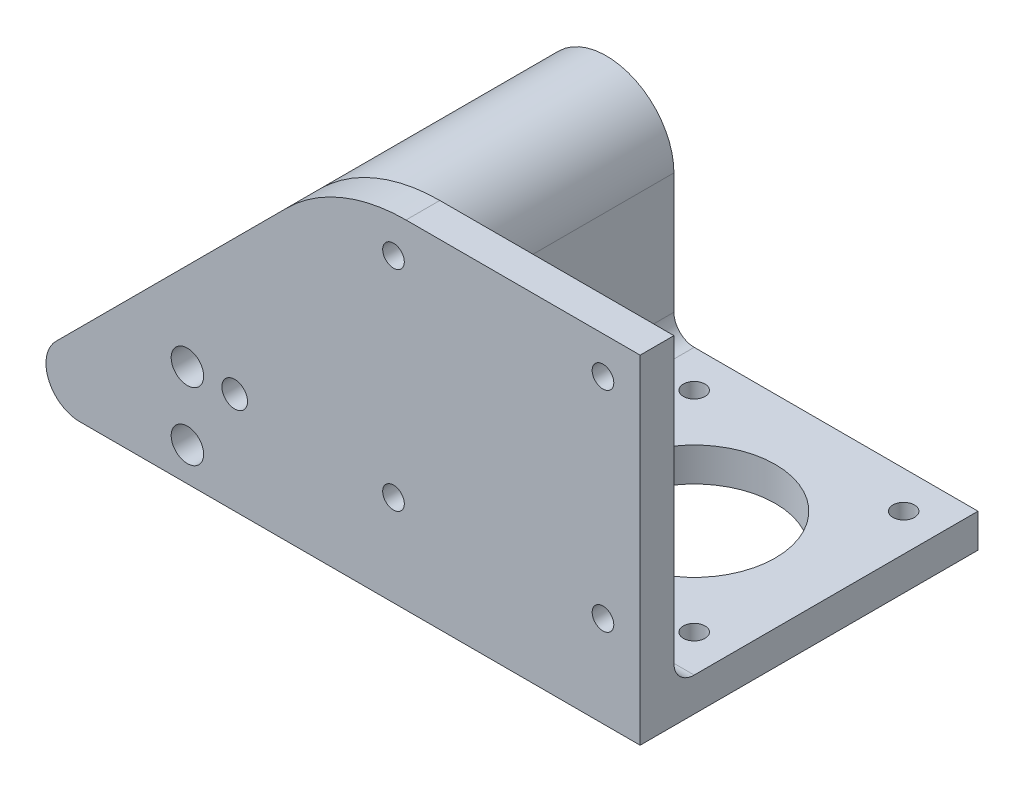
SolidWorks part; units mm, degrees
ref_plane "前视基准面" through (0, 0, 0) normal (0, 0, 1) x (1, 0, 0)
ref_plane "上视基准面" through (0, 0, 0) normal (0, 1, 0) x (1, 0, 0)
ref_plane "右视基准面" through (0, 0, 0) normal (1, 0, 0) x (0, 0, -1)
sketch "草图1" plane through (0, 0, 0) normal (0, 1, 0) x (1, 0, 0)
  line L0 (-24, -24) -> (-24, 21)
  line L1 (-21, -21) -> (21, -21) construction
  line L2 (-21, -21) -> (-21, 21) construction
  line L3 (-21, 21) -> (21, 21)
  line L4 (21, -21) -> (21, 21)
  line L5 (-21, -21) -> (21, 21) construction
  line L6 (-21, 21) -> (21, -21) construction
  line L7 (-15.5, -15.5) -> (15.5, -15.5) construction
  line L8 (-15.5, -15.5) -> (-15.5, 15.5) construction
  line L9 (-15.5, 15.5) -> (15.5, 15.5) construction
  line L10 (15.5, -15.5) -> (15.5, 15.5) construction
  line L11 (-15.5, -15.5) -> (15.5, 15.5) construction
  line L12 (-15.5, 15.5) -> (15.5, -15.5) construction
  line L13 (-21, -21) -> (21, -21) construction
  line L15 (-24, -24) -> (21, -24)
  line L16 (21, -21) -> (21, -24)
  line L17 (-24, 21) -> (-21, 21)
  circle A0 centre (-15.5, 15.5) radius 1.6
  circle A1 centre (15.5, 15.5) radius 1.6
  circle A2 centre (-15.5, -15.5) radius 1.6
  circle A3 centre (15.5, -15.5) radius 1.6
  circle A4 centre (0, 0) radius 12
  point P0 (0, 0)
  point P12 (0, 0)
  dimension "D3" = 3.2
  dimension "D4" = 3.2
  dimension "D5" = 3.2
  dimension "D6" = 3.2
  dimension "D9" = 24
  dimension "D1" = 42
  dimension "D2" = 42
  dimension "D7" = 31
  dimension "D8" = 3
  dimension "D10" = 3
extrude "凸台-拉伸1" add sketch "草图1" along normal blind 5
sketch "草图4" plane through (0, 0, 24) normal (0, 0, 1) x (1, 0, 0)
  line L0 (-21, 8) -> (21, 8) construction
  line L1 (-24, 0) -> (21, 0)
  line L2 (-24, 0) -> (-24, 50)
  line L3 (-24, 50) -> (21, 50)
  line L4 (21, 0) -> (21, 50)
  line L5 (21, 8) -> (-21, 50) construction
  line L6 (-21, 8) -> (21, 50) construction
  line L7 (21, 5) -> (21, 0) construction
  line L8 (-15.5, 13.5) -> (15.5, 13.5) construction
  line L9 (-15.5, 13.5) -> (-15.5, 44.5) construction
  line L10 (-15.5, 44.5) -> (15.5, 44.5) construction
  line L11 (15.5, 13.5) -> (15.5, 44.5) construction
  line L12 (-15.5, 13.5) -> (15.5, 44.5) construction
  line L13 (-15.5, 44.5) -> (15.5, 13.5) construction
  line L14 (-21, 50) -> (-21, 8) construction
  line L15 (-16, 29) -> (16, 29) construction
  circle A0 centre (-15.5, 44.5) radius 1.6
  circle A1 centre (15.5, 44.5) radius 1.6
  circle A2 centre (-15.5, 13.5) radius 1.6
  circle A3 centre (15.5, 13.5) radius 1.6
  point P7 (0, 29)
  dimension "D4" = 3.2
  dimension "D5" = 3.2
  dimension "D6" = 3.2
  dimension "D7" = 3.2
  dimension "D1" = 50
  dimension "D2" = 42
  dimension "D3" = 31
  dimension "D8" = 42
extrude "凸台-拉伸4" add sketch "草图4" along normal blind 5
sketch "草图5" plane through (-24, 0, 0) normal (-1, 0, 0) x (0, 0, 1)
  line L1 (29, 50) -> (-21, 50)
  line L2 (29, 50) -> (29, 0)
  line L3 (29, 0) -> (-21, 0)
  line L4 (-21, 50) -> (-21, 0)
extrude "凸台-拉伸5" add sketch "草图5" along normal blind 50
sketch "草图6" plane through (0, 0, -21) normal (0, 0, -1) x (-1, 0, 0)
  circle A0 centre (39, 15) radius 1.5 construction
  circle A1 centre (46, 5) radius 2 construction
  circle A2 centre (46, 15) radius 2 construction
  circle A3 centre (39, 15) radius 1.5 construction
  circle A4 centre (46, 5) radius 2 construction
  circle A5 centre (46, 15) radius 2 construction
  circle A6 centre (46, 15) radius 2.4
  circle A7 centre (39, 15) radius 1.9
  circle A8 centre (46, 5) radius 2.4
  dimension "D1" = 0.4
extrude "切除-拉伸1" cut sketch "草图6" against normal through all
sketch "草图7" plane through (0, 0, -21) normal (0, 0, -1) x (-1, 0, 0)
  line L0 (-21, 0) -> (74, 0) construction
  line L1 (51, 0) -> (34, 0)
  line L2 (51, 0) -> (51, 20)
  line L3 (51, 20) -> (34, 20)
  line L4 (34, 0) -> (34, 20)
  line L5 (24, 50) -> (24, 5) construction
  dimension "D1" = 20
  dimension "D2" = 10
  dimension "D3" = 17
extrude "切除-拉伸2" cut sketch "草图7" against normal offset from surface (45 mm away) 5 up to face at (-48.4, 5, 29)
sketch "草图8" plane through (0, 0, 0) normal (0, -1, 0) x (1, 0, 0)
  circle A0 centre (-60.5, 19) radius 1.8 construction
  circle A1 centre (-60.5, 19) radius 1.8
extrude "切除-拉伸3" cut sketch "草图8" against normal through all
sketch "草图9" plane through (0, 50, 0) normal (0, 1, 0) x (1, 0, 0)
  circle A0 centre (-60.5, -19) radius 1.8 construction
  circle A1 centre (-60.5, -19) radius 1.8 construction
  circle A2 centre (-60.5, -19) radius 2.8
  dimension "D1" = 1
extrude "切除-拉伸4" cut sketch "草图9" against normal offset from surface (45 mm away) 5 up to face at (-60.5, 0, 17.2)
chamfer "倒角1" distance 50 angle 45 1 edges at (-74, 50, 4)
fillet "圆角1" radius 5 1 edges at (-74, 0, 4)
fillet "圆角2" radius 10 1 edges at (-24, 50, 1.5) type face fillet first side face at (-40.5858, 33.4142, 8) second side face at (-24, 27.5, 1.5)
fillet "圆角4" radius 25 1 edges at (-24, 50, 26.5)
fillet "圆角5" radius 3 6 edges at (-1.5, 5, 24) (-24, 5, 1.5) (-30.1732, 35.0967, 24) (-24, 15.4289, 24) (-34, 20, 1.5) (-51, 20, 1.5)
fillet "圆角6" radius 1.5 5 edges at (-34, 8.5, 24) (-34.8787, 19.1213, 24) (-42.5, 20, 24) (-50.1213, 19.1213, 24) (-51, 8.5, 24)
